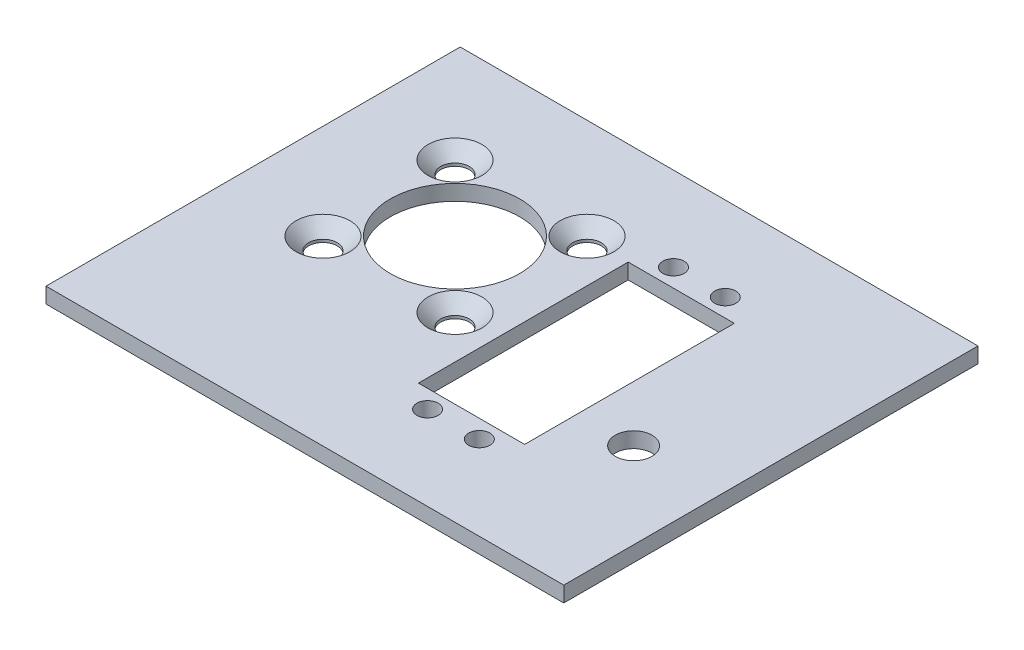
SolidWorks part; units mm, degrees
ref_plane "Płaszczyzna przednia" through (0, 0, 0) normal (0, 0, 1) x (1, 0, 0)
ref_plane "Płaszczyzna górna" through (0, 0, 0) normal (0, 1, 0) x (1, 0, 0)
ref_plane "Płaszczyzna prawa" through (0, 0, 0) normal (1, 0, 0) x (0, 0, -1)
sketch "Szkic1" plane through (0, 0, 0) normal (0, 1, 0) x (1, 0, 0)
  line L6 (-20.2688, 11.7569) -> (5.2312, -13.7431) construction
  line L11 (-38.6633, 31.161) -> (61.3367, 31.161)
  line L12 (-38.6633, 31.161) -> (-38.6633, -48.839)
  line L13 (-38.6633, -48.839) -> (61.3367, -48.839)
  line L14 (61.3367, 31.161) -> (61.3367, -48.839)
  line L15 (-20.2688, -13.7431) -> (5.2312, 11.7569) construction
  line L17 (13.5251, 11.411) -> (34.0251, 11.411)
  line L18 (13.5251, 11.411) -> (13.5251, -29.089)
  line L23 (13.5251, -29.089) -> (34.0251, -29.089)
  line L24 (34.0251, 11.411) -> (34.0251, -29.089)
  circle A0 centre (-7.5188, -0.9931) radius 12.5
  circle A2 centre (-20.2688, 11.7569) radius 2.55
  circle A3 centre (5.2312, 11.7569) radius 2.55
  circle A4 centre (5.2312, -13.7431) radius 2.55
  circle A5 centre (-20.2688, -13.7431) radius 2.55
  circle A6 centre (18.7751, 14.911) radius 2.05
  circle A7 centre (28.7751, 14.911) radius 2.05
  circle A8 centre (18.7751, -32.589) radius 2.05
  circle A9 centre (28.7751, -32.589) radius 2.05
  circle A10 centre (23.7751, -18.789) radius 0.5
  circle A11 centre (-7.5188, -0.9931) radius 0.5
  circle A12 centre (44.7751, -18.789) radius 3.55
  circle A13 centre (44.7751, -18.789) radius 0.5
  point P18 (23.7751, -29.089)
  point P22 (23.7751, 11.411)
  dimension "D3" = 10.3
  dimension "D5" = 3.5
  dimension "D13" = 36
  dimension "D18" = 19.75
  dimension "D20" = 5.1
  dimension "D22" = 25
  dimension "D23" = 7.1
  dimension "D24" = 4.1
  dimension "D25" = 47.5
  dimension "D1" = 100
  dimension "D2" = 80
  dimension "D4" = 10.25
  dimension "D6" = 3.5
  dimension "D7" = 5
  dimension "D8" = 5
  dimension "D9" = 3.5
  dimension "D10" = 3.5
  dimension "D11" = 5
  dimension "D12" = 5
  dimension "D14" = 21
  dimension "D15" = 40.5
  dimension "D16" = 20.5
  dimension "D17" = 10.3
  dimension "D19" = 19.75
  dimension "D21" = 25.5
extrude "Dodanie-wyciągnięcie1" add sketch "Szkic1" along normal blind 3 contours L14 L11 L12 L13 A12 A9 A8 A7 A6 A5 A4 A3 A2 A0 L17 L24 L23 L18 region at (11.1044, 0, 9.469)
sketch "Sketch1" plane through (0, 0, 0) normal (0, 1, 0) x (1, 0, 0)
  point P0 (-20.2688, -13.7431)
  point P3 (5.2312, -13.7431)
  point P6 (5.2312, 11.7569)
  point P9 (-20.2688, 11.7569)
sketch "Sketch3" plane through (0, 3, 0) normal (0, 1, 0) x (1, 0, 0)
  point P0 (-20.2688, -13.7431)
  point P3 (5.2312, -13.7431)
  point P6 (5.2312, 11.7569)
  point P9 (-20.2688, 11.7569)
hole_wizard "CSK for M5 Countersunk Flat Head Screw2" positions "Sketch3" profile "Sketch4" countersink size "M5" standard "ISO" end condition through all
sketch "Sketch4" plane through (-20.2688, 3, 13.7431) normal (1, 0, 0) x (0, 0, 1)
  line L0 (0, 0) -> (0, 3)
  line L1 (0, 3) -> (2.75, 3)
  line L2 (2.75, 3) -> (2.75, 2.45)
  line L3 (2.75, 2.45) -> (5.2, 0)
  line L5 (5.2, 0) -> (0, 0)
  line L6 (-2.75, 2.45) -> (-5.2, 0) construction
  line L11 (0, -6.35) -> (0, 107.95) construction
  dimension "Thru Hole Dia." = 5.5
  dimension "Thru Hole Depth" = 3
  dimension "Near C'Sink Dia." = 10.4
  dimension "Near C'Sink Angle" = 90
